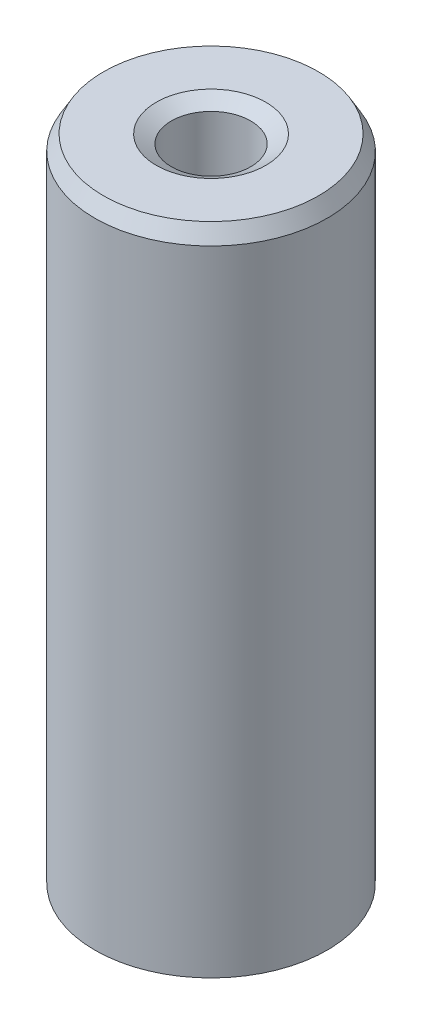
SolidWorks part; units mm, degrees
ref_plane "Front Plane" through (0, 0, 0) normal (0, 0, 1) x (1, 0, 0)
ref_plane "Top Plane" through (0, 0, 0) normal (0, 1, 0) x (1, 0, 0)
ref_plane "Right Plane" through (0, 0, 0) normal (1, 0, 0) x (0, 0, -1)
sketch "Sketch1" plane through (0, 0, 0) normal (0, 1, 0) x (1, 0, 0)
  circle A0 centre (0, 0) radius 12.5
  dimension "SLEEVE_OD" = 25
extrude "Boss-Extrude1" add sketch "Sketch1" along normal blind 70.7378
sketch "Sketch2" plane through (0, 0, 0) normal (0, 1, 0) x (1, 0, 0)
  circle A0 centre (0, 0) radius 4.2718
  dimension "BORE_D" = 8.5436
extrude "Cut-Extrude1" cut sketch "Sketch2" along normal through all
chamfer "Chamfer1" distance 1.6196 angle 30 4 edges at (0, 70.7378, 4.2718) (0, 0, 4.2718) (0, 0, 12.5) (0, 70.7378, 12.5) first distance on face at (0, 70.7378, 4.2718) first distance on face at (0, 0, 4.2718) first distance on face at (0, 70.7378, 12.5)
